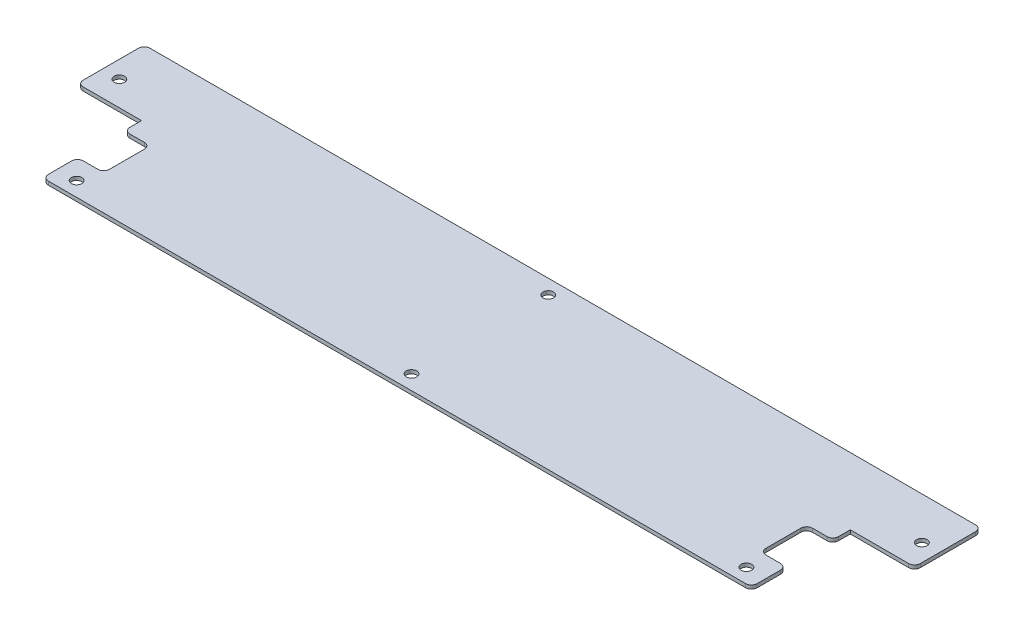
SolidWorks part; units mm, degrees
ref_plane "Front Plane" through (0, 0, 0) normal (0, 0, 1) x (1, 0, 0)
ref_plane "Top Plane" through (0, 0, 0) normal (0, 1, 0) x (1, 0, 0)
ref_plane "Right Plane" through (0, 0, 0) normal (1, 0, 0) x (0, 0, -1)
sketch "Sketch1" plane through (0, 0, 0) normal (0, 1, 0) x (1, 0, 0)
  line L0 (0, 0) -> (0, -29.845) construction
  line L1 (190.5, -36.195) -> (-190.5, -36.195) construction
  line L2 (190.5, -36.195) -> (190.5, 36.195) construction
  line L3 (190.5, 36.195) -> (-190.5, 36.195) construction
  line L4 (-190.5, -36.195) -> (-190.5, 36.195) construction
  line L5 (190.5, -36.195) -> (-190.5, 36.195) construction
  line L6 (190.5, 36.195) -> (-190.5, -36.195) construction
  line L7 (-146.177, -29.845) -> (146.177, -29.845) construction
  line L8 (0, 0) -> (0, 29.845) construction
  line L27 (0, 0) -> (0, 17.78) construction
  line L34 (-175.1457, 17.78) -> (175.1457, 17.78) construction
  line L35 (-154.686, -36.195) -> (-154.686, 6.985)
  line L48 (154.686, -36.195) -> (154.686, 6.985)
  line L49 (154.686, -36.195) -> (-154.686, -36.195)
  line L50 (-154.686, 6.985) -> (-182.7083, 6.985)
  line L52 (-182.7083, 36.195) -> (-182.7083, 6.985)
  line L53 (-182.7083, 36.195) -> (182.7083, 36.195)
  line L54 (182.7083, 36.195) -> (182.7083, 6.985)
  line L55 (182.7083, 6.985) -> (154.686, 6.985)
  circle A0 centre (175.1457, 17.78) radius 2.286
  circle A1 centre (0, 29.845) radius 2.286
  circle A2 centre (146.177, -29.845) radius 2.286
  circle A3 centre (-175.1457, 17.78) radius 2.286
  circle A4 centre (0, -29.845) radius 2.286
  circle A5 centre (-146.177, -29.845) radius 2.286
  point P0 (0, 0)
  point P10 (0, -29.845)
  point P21 (0, 36.195)
  point P22 (0, -36.195)
  point P58 (0, 17.78)
  dimension "D5" = 4.572
  dimension "D1" = 381
  dimension "D2" = 72.39
  dimension "D3" = 7.5626
  dimension "D4" = 8.509
  dimension "D6" = 29.845
  dimension "D7" = 17.78
  dimension "D8" = 35.814
  dimension "D10" = 6.35
  dimension "D11" = 43.18
  dimension "D12" = 43.18
  dimension "D13" = 28.0223
  dimension "D14" = 175.1457
  dimension "D15" = 175.1457
  dimension "D16" = 182.7083
  dimension "D17" = 182.7083
extrude "Boss-Extrude1" add sketch "Sketch1" along normal blind 1.5875
fillet "Fillet1" radius 2.54 6 edges at (182.7083, 0.7937, -6.985) (182.7083, 0.7937, -36.195) (154.686, 0.7937, 36.195) (-154.686, 0.7937, 36.195) (-182.7083, 0.7937, -36.195) (-182.7083, 0.7937, -6.985)
sketch "Sketch2" plane through (0, 1.5875, 0) normal (0, 1, 0) x (1, 0, 0)
  line L0 (-154.686, 6.985) -> (-154.686, -33.655) construction
  line L1 (-154.686, -0.635) -> (-143.256, -0.635)
  line L2 (-154.686, -0.635) -> (-154.686, -20.955)
  line L3 (-154.686, -20.955) -> (-143.256, -20.955)
  line L4 (-143.256, -0.635) -> (-143.256, -20.955)
  line L5 (154.686, -33.655) -> (154.686, 6.985) construction
  line L6 (154.686, -0.635) -> (143.256, -0.635)
  line L7 (154.686, -0.635) -> (154.686, -20.955)
  line L8 (154.686, -20.955) -> (143.256, -20.955)
  line L9 (143.256, -0.635) -> (143.256, -20.955)
  line L10 (-152.146, -36.195) -> (152.146, -36.195) construction
  point P12 (-135.5914, 1.051)
  point P15 (-144.526, -8.255)
  point P16 (-144.526, -8.255)
  point P17 (0, 0)
  point P18 (-143.6804, -8.255)
  dimension "D1" = 20.32
  dimension "D2" = 15.24
  dimension "D3" = 11.43
  dimension "D4" = 20.32
  dimension "D5" = 15.24
extrude "Cut-Extrude1" cut sketch "Sketch2" against normal blind 2.54
fillet "Fillet2" radius 2.54 8 edges at (154.686, 0.7937, 20.955) (143.256, 0.7937, 20.955) (143.256, 0.7937, 0.635) (154.686, 0.7937, 0.635) (-154.686, 0.7937, 20.955) (-143.256, 0.7937, 20.955) (-143.256, 0.7937, 0.635) (-154.686, 0.7937, 0.635)
